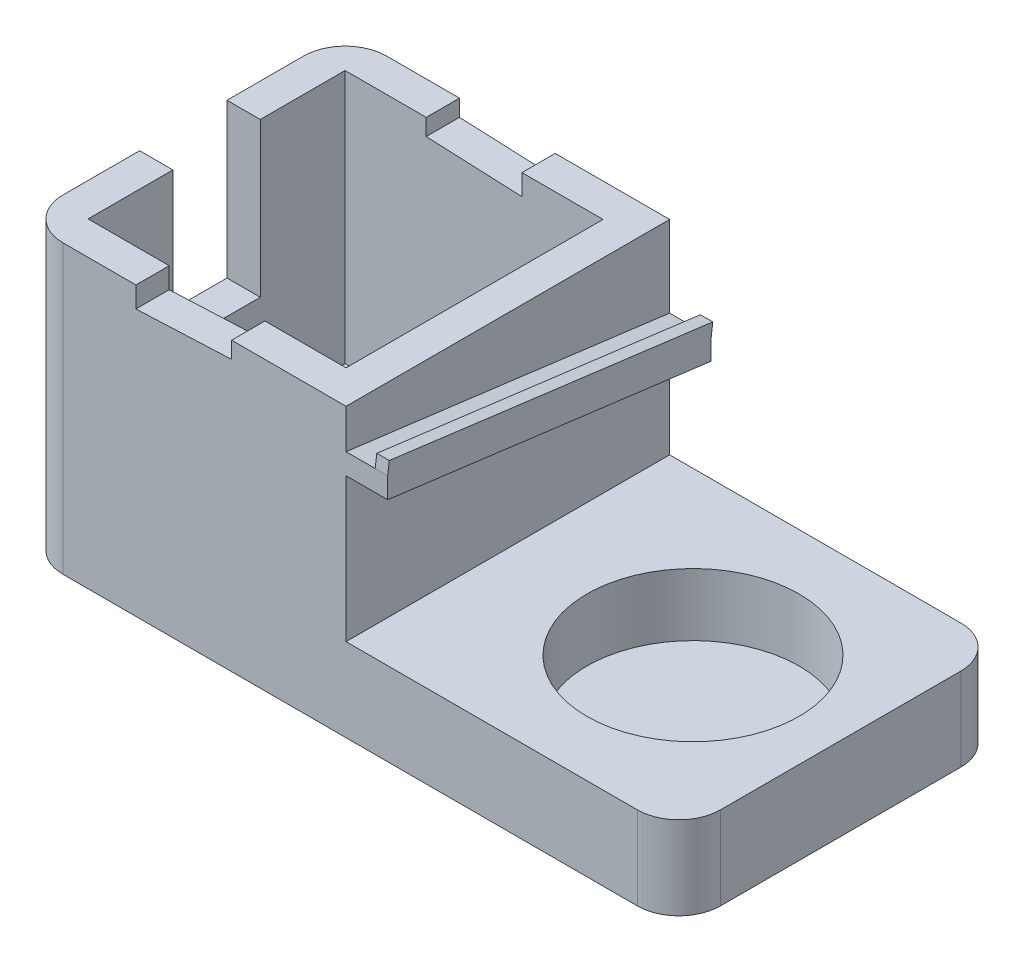
SolidWorks part; units mm, degrees
ref_plane "Front Plane" through (0, 0, 0) normal (0, 0, 1) x (1, 0, 0)
ref_plane "Top Plane" through (0, 0, 0) normal (0, 1, 0) x (1, 0, 0)
ref_plane "Right Plane" through (0, 0, 0) normal (1, 0, 0) x (0, 0, -1)
sketch "Sketch1" plane through (0, 0, 0) normal (0, 1, 0) x (1, 0, 0)
  line L1 (0, 0) -> (62, 0)
  line L2 (0, 0) -> (0, 61.7705)
  line L3 (0, 61.7705) -> (62, 61.7705)
  line L4 (62, 0) -> (62, 61.7705)
  line L9 (-8, -8) -> (70, -8)
  line L10 (-8, -8) -> (-8, 69.7705)
  line L11 (-8, 69.7705) -> (70, 69.7705)
  line L12 (70, -8) -> (70, 69.7705)
  circle A0 centre (31, 31) radius 22.5
  circle A1 centre (31, 31) radius 27.5
  circle A4 centre (5.6569, 56.1137) radius 2
  circle A5 centre (5.6569, 56.1137) radius 4
  circle A6 centre (56.3431, 56.1137) radius 2
  circle A7 centre (56.3431, 56.1137) radius 4
  circle A8 centre (56.3431, 5.6569) radius 4
  circle A9 centre (5.6569, 5.6569) radius 4
  circle A10 centre (5.6569, 5.6569) radius 2
  circle A11 centre (56.3431, 5.6569) radius 2
  dimension "D1" = 62
  dimension "D3" = 31
  dimension "D4" = 5
  dimension "D6" = 8
  dimension "D2" = 8
  dimension "D5" = 8
  dimension "D7" = 8
extrude "Boss-Extrude6" add sketch "Sketch1" along normal blind 8 contours L1 L4 L3 L2 A7 A1 A5 A8 A9 | A10 | A9 A10 | A11 | A8 A11 | A6 | A7 A6 | A4 | A5 A4 | A1 A0 | A0 region at (0.8752, 0, -30.8853) region at (31, 0, -31) region at (4.2778, 0, -31) region at (5.6569, 0, -56.1137) region at (1.77, 0, -56.1137) region at (56.3431, 0, -56.1137) region at (52.4563, 0, -56.1137) region at (52.4563, 0, -5.6569) region at (1.77, 0, -5.6569) region at (5.6569, 0, -5.6569) region at (56.3431, 0, -5.6569)
extrude "Boss-Extrude9" add sketch "Sketch1<15>" along normal blind 69 contours L3 L4 L1 L2 | L12 L11 L10 L9
sketch "Sketch1<15>" plane through (0, 0, 0) normal (0, 1, 0) x (1, 0, 0) same geometry as "Sketch1"
extrude "Cut-Extrude2" cut sketch "Sketch1<17>" along normal blind 56 contours A9 | A8 | A7 | A5
sketch "Sketch1<17>" plane through (0, 0, 0) normal (0, 1, 0) x (1, 0, 0) same geometry as "Sketch1"
extrude "Boss-Extrude10" add sketch "Sketch1<18>" along normal blind 4 contours A11 | A8 | A10 | A9 | A4 | A5 | A6 | A7
sketch "Sketch1<18>" plane through (0, 0, 0) normal (0, 1, 0) x (1, 0, 0) same geometry as "Sketch1"
ref_plane "Plane2" through (0, 0, -69.7705) normal (0, 0, -1) x (-1, 0, 0)
sketch "Sketch3" plane through (0, 0, -69.7705) normal (0, 0, -1) x (-1, 0, 0)
  line L15 (8, 69) -> (-70, 69) construction
  line L17 (-42.5, 69) -> (-42.5, 64)
  line L18 (-42.5, 64) -> (-19.5, 65)
  line L19 (-19.5, 65) -> (-19.5, 69)
  line L20 (-42.5, 69) -> (-19.5, 69)
  dimension "D1" = 5
  dimension "D2" = 4
ref_plane "Plane3" through (0, 0, 8) normal (0, 0, 1) x (1, 0, 0)
ref_plane "Plane4" through (-8, 0, 0) normal (-1, 0, 0) x (0, 0, 1)
sketch "Sketch6" plane through (-8, 0, 0) normal (-1, 0, 0) x (0, 0, 1)
  line L8 (8, 69) -> (-69.7705, 69) construction
  line L22 (-41.3853, 69) -> (-41.3853, 32)
  line L25 (-20.3853, 32) -> (-20.3853, 69)
  line L28 (-41.3853, 69) -> (-20.3853, 69)
  line L30 (-41.3853, 32) -> (-20.3853, 32)
  point P9 (-33.4083, 56)
  dimension "D1" = 21
  dimension "D2" = 37
extrude "Cut-Extrude10" cut sketch "Sketch3" against normal blind 8
sketch "Sketch9" plane through (0, 0, 8) normal (0, 0, 1) x (1, 0, 0)
  line L1 (-8, 69) -> (70, 69) construction
  line L3 (19.5, 69) -> (19.5, 64)
  line L4 (19.5, 64) -> (42.5, 65)
  line L5 (42.5, 65) -> (42.5, 69)
  line L6 (19.5, 69) -> (42.5, 69)
  dimension "D1" = 5
  dimension "D2" = 4
extrude "Cut-Extrude11" cut sketch "Sketch9" against normal blind 8
extrude "Cut-Extrude13" cut sketch "Sketch6" against normal blind 10
ref_plane "Plane5" through (-8, 0, 0) normal (-1, 0, 0) x (0, 0, 1)
sketch "Sketch10" plane through (-8, 0, 0) normal (-1, 0, 0) x (0, 0, 1)
  line L0 (-69.7705, 20) -> (8, 20)
  line L1 (-69.7705, 69) -> (-69.7705, 0) construction
  line L2 (8, 69) -> (8, 0) construction
  line L3 (8, 20) -> (8, 0)
  line L4 (8, 0) -> (-69.7705, 0)
  line L5 (-69.7705, 0) -> (-69.7705, 20)
  dimension "D1" = 20
ref_plane "Plane6" through (70, 0, 0) normal (1, 0, 0) x (0, 0, -1)
sketch "Sketch12" plane through (70, 0, 0) normal (1, 0, 0) x (0, 0, -1)
  line L0 (69.7705, 69) -> (69.7705, 0) construction
  line L1 (-8, 0) -> (69.7705, 0)
  line L2 (-8, 0) -> (-8, 20)
  line L3 (-8, 20) -> (69.7705, 20)
  line L4 (69.7705, 0) -> (69.7705, 20)
  dimension "D1" = 20
extrude "Boss-Extrude12" add sketch "Sketch12" along normal blind 80
sketch "Sketch13" plane through (70, 0, 0) normal (1, 0, 0) x (0, 0, -1)
  line L0 (-8, 59.5393) -> (69.7705, 49.5)
  line L1 (-8, 69) -> (-8, 20) construction
  line L2 (69.7705, 69) -> (69.7705, 20) construction
  line L3 (69.7705, 49.5) -> (69.7705, 44.5)
  line L4 (69.7705, 44.5) -> (-8, 54.5393)
  line L5 (-8, 54.5393) -> (-8, 59.5393)
extrude "Boss-Extrude13" add sketch "Sketch13" along normal blind 10
ref_plane "Plane7" through (0, 57.5476, -7.4288) normal (0, 0.9918, -0.128) x (1, 0, 0)
sketch "Sketch14" plane through (0, 57.5476, -7.4288) normal (0, 0.9918, -0.128) x (1, 0, 0)
  line L0 (77, 62.859) -> (80, 62.859)
  line L1 (80, 62.859) -> (70, 62.859) construction
  line L2 (80, 62.859) -> (80, -15.5568)
  line L3 (80, -15.5568) -> (77, -15.5568)
  line L4 (80, -15.5568) -> (70, -15.5568) construction
  line L5 (77, -15.5568) -> (77, 62.859)
  dimension "D1" = 3
extrude "Boss-Extrude14" add sketch "Sketch14" along normal blind 3
ref_plane "Plane8" through (0, 20, 0) normal (0, 1, 0) x (1, 0, 0)
sketch "Sketch15" plane through (0, 20, 0) normal (0, 1, 0) x (1, 0, 0)
  line L0 (150, 30.8853) -> (114.5, 30.8853)
  line L1 (150, 69.7705) -> (150, -8) construction
  circle A0 centre (114.5, 30.8853) radius 25.5
  dimension "D1" = 35.5
extrude "Cut-Extrude14" cut sketch "Sketch15" against normal blind 15 contours A0 region at (89.7212, 20, -30.8853)
fillet "Fillet1" radius 10 4 edges at (-8, 34.5, -69.7705) (-8, 34.5, 8) (150, 10, -69.7705) (150, 10, 8)
